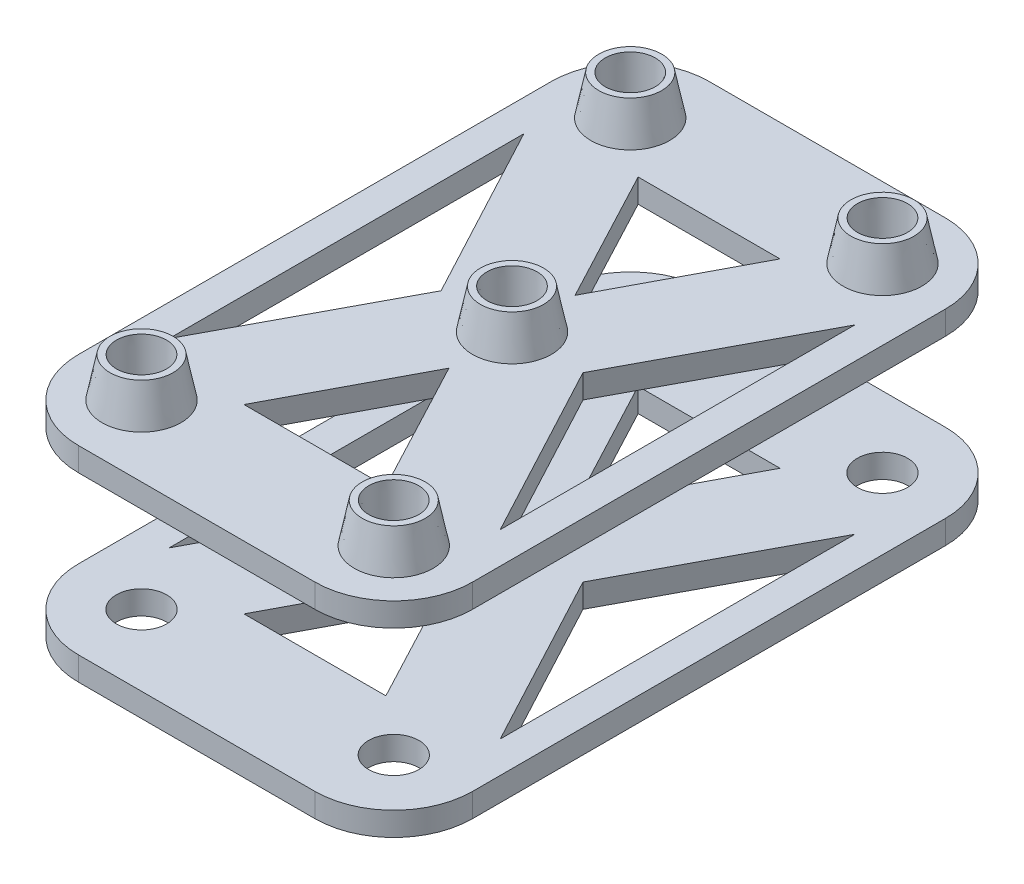
SolidWorks part; units mm, degrees
ref_plane "Front Plane" through (0, 0, 0) normal (0, 0, 1) x (1, 0, 0)
ref_plane "Top Plane" through (0, 0, 0) normal (0, 1, 0) x (1, 0, 0)
ref_plane "Right Plane" through (0, 0, 0) normal (1, 0, 0) x (0, 0, -1)
sketch "Sketch2" plane through (0, 0, 0) normal (0, 1, 0) x (1, 0, 0)
  line L0 (0, 0) -> (0, 12.8086) construction
  line L1 (25, -40) -> (-25, -40)
  line L2 (25, -40) -> (25, 40)
  line L3 (25, 40) -> (-25, 40)
  line L4 (-25, -40) -> (-25, 40)
  line L5 (25, -40) -> (-25, 40) construction
  line L6 (25, 40) -> (-25, -40) construction
  line L7 (0, 0) -> (9.0161, 0) construction
  point P0 (0, 0)
  dimension "D1" = 80
  dimension "D2" = 50
extrude "Boss-Extrude1" add sketch "Sketch2" against normal blind 3 contours L4 L1 L2 L3 region at (0, 0, 0)
sketch "Sketch3" plane through (0, 0, 0) normal (0, 1, 0) x (1, 0, 0)
  line L0 (0, 0) -> (17.9546, 0) construction
  line L1 (0, 0) -> (0, 17.9015) construction
  line L2 (25, 40) -> (-25, 40) construction
  line L3 (-25, -40) -> (-25, 40) construction
  circle A0 centre (-16, 31) radius 3
  circle A1 centre (-16, 31) radius 5
  circle A2 centre (16, 31) radius 3
  circle A3 centre (16, 31) radius 5
  circle A4 centre (16, -31) radius 3
  circle A5 centre (16, -31) radius 5
  circle A6 centre (-16, -31) radius 3
  circle A7 centre (-16, -31) radius 5
  circle A8 centre (0, 0) radius 3
  circle A9 centre (0, 0) radius 5
  point P24 (0, 0)
  dimension "D1" = 6
  dimension "D2" = 10
  dimension "D5" = 6
  dimension "D6" = 10
  dimension "D3" = 9
  dimension "D4" = 9
extrude "Boss-Extrude2" add sketch "Sketch3" along normal blind 5
chamfer "Chamfer1" distance 5 distance2 1 5 edges at (16, 5, 36) (16, 5, -36) (-16, 5, -26) (0, 5, 5) (-16, 5, 26) first distance on face at (16, 5, 36) first distance on face at (16, 5, -36) first distance on face at (-16, 5, -26) first distance on face at (0, 5, 5) first distance on face at (-16, 5, 26)
sketch "Sketch4" plane through (0, 0, 0) normal (0, 1, 0) x (1, 0, 0)
  line L0 (-21, 22.5) -> (-21, -22.5)
  line L1 (-21, -22.5) -> (-9, 0)
  line L2 (-9, 0) -> (-21, 22.5)
  line L3 (-25, -40) -> (-25, 40) construction
  line L4 (0, 0) -> (0, -40) construction
  line L5 (25, -40) -> (-25, -40) construction
  line L6 (9, 0) -> (21, 22.5)
  line L7 (21, 22.5) -> (21, -22.5)
  line L8 (21, -22.5) -> (9, 0)
  line L9 (0, 8) -> (9, 25)
  line L10 (9, 25) -> (-9, 25)
  line L11 (-9, 25) -> (0, 8)
  line L12 (25, 40) -> (-25, 40) construction
  line L13 (0, 0) -> (-25, 0) construction
  line L14 (0, -8) -> (9, -25)
  line L15 (9, -25) -> (-9, -25)
  line L16 (-9, -25) -> (0, -8)
  point P8 (-21, 0)
  dimension "D1" = 4
  dimension "D2" = 12
  dimension "D3" = 45
  dimension "D4" = 15
  dimension "D5" = 17
extrude "Cut-Extrude1" cut sketch "Sketch4" against normal up to surface (3 mm away) up to face at (0, -3, 0)
fillet "Fillet1" radius 10 4 edges at (-25, -1.5, 40) (25, -1.5, 40) (25, -1.5, -40) (-25, -1.5, -40)
draft "Draft3" type of draft neutral plane draft angle 2 faces to draft 5 face at (16, 5, -34) face at (-16, 5, -28) face at (-16, 5, 28) face at (0, 5, 3) face at (16, 5, 34) neutral plane through (0, 0, 0) neutral plane normal (0, 1, 0) parameters "D1"=2
ref_plane "Plane1" through (0, -13, 0) normal (0, -1, 0) x (-1, 0, 0)
mirror "Mirror5" about plane through (0, -13, 0) normal (0, -1, 0) of bodies 103
sketch "Sketch5" plane through (0, -31, 0) normal (0, -1, 0) x (1, 0, 0)
  line L1 (25, -40) -> (-25, -40)
  line L2 (25, -40) -> (25, 40)
  line L3 (25, 40) -> (-25, 40)
  line L4 (-25, -40) -> (-25, 40)
  line L5 (25, -40) -> (-25, 40) construction
  line L6 (25, 40) -> (-25, -40) construction
  point P0 (0, 0)
  dimension "D1" = 50
  dimension "D2" = 80
extrude "Cut-Extrude2" cut sketch "Sketch5" against normal up to surface (5 mm away) up to face at (17, -26, 0)
sketch "Sketch6" plane through (0, -26, 0) normal (0, -1, 0) x (1, 0, 0)
  line L0 (15, 40) -> (-15, 40) construction
  line L1 (-25, 30) -> (-25, -30) construction
  line L2 (0, 0) -> (0, -40) construction
  line L3 (15, -40) -> (-15, -40) construction
  line L4 (0, 0) -> (-25, 0) construction
  circle A0 centre (-16, 31) radius 3.2
  circle A4 centre (0, 0) radius 3.2
  circle A5 centre (-16, -31) radius 3.2
  circle A6 centre (16, 31) radius 3.2
  circle A7 centre (16, -31) radius 3.2
  dimension "D3" = 6.4
  dimension "D4" = 6.4
  dimension "D1" = 9
  dimension "D2" = 9
extrude "Cut-Extrude4" cut sketch "Sketch6" against normal up to surface (3 mm away) up to face at (17, -23, 0)
